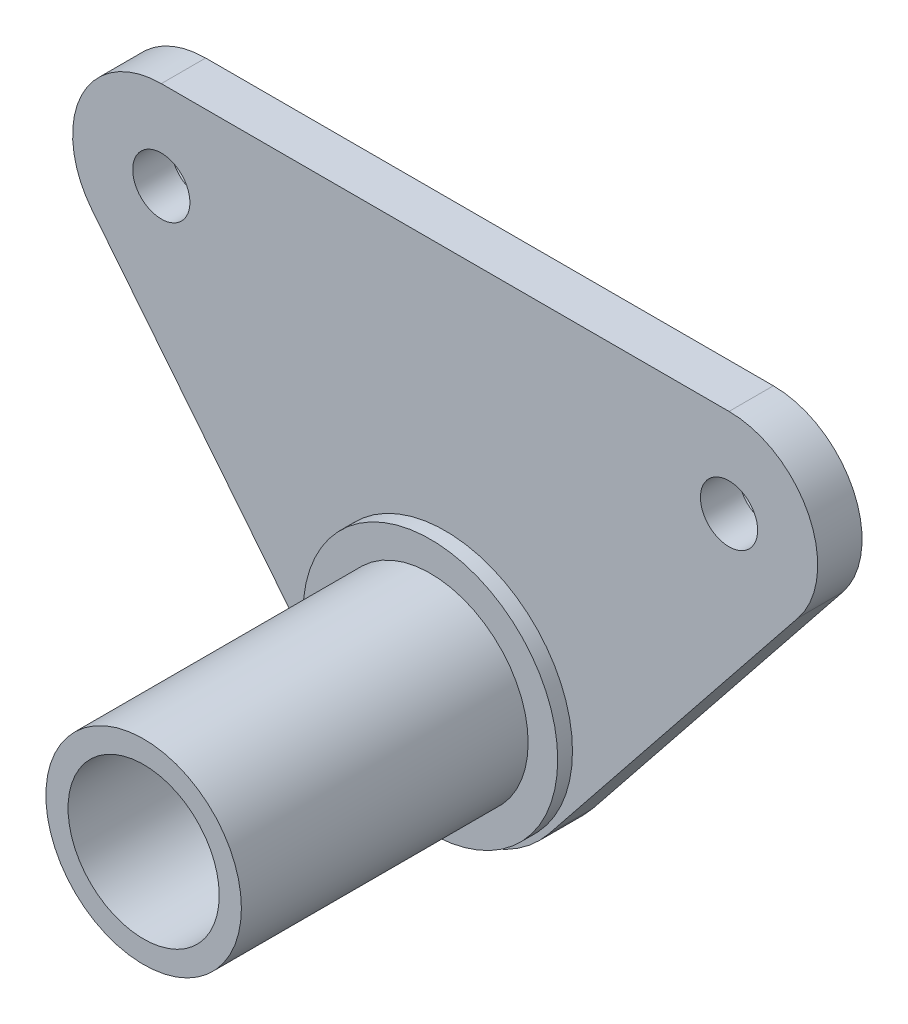
SolidWorks part; units mm, degrees
ref_plane "Front Plane" through (0, 0, 0) normal (0, 0, 1) x (1, 0, 0)
ref_plane "Top Plane" through (0, 0, 0) normal (0, 1, 0) x (1, 0, 0)
ref_plane "Right Plane" through (0, 0, 0) normal (1, 0, 0) x (0, 0, -1)
sketch "Sketch1" plane through (0, 0, 0) normal (0, 0, 1) x (1, 0, 0)
  line L0 (-24.39, 32.01) -> (24.39, 32.01)
  line L1 (-24.39, 28.2) -> (24.39, 28.2) construction
  line L2 (-28.2, 24.39) -> (-28.2, -24.39) construction
  line L3 (-24.39, -28.2) -> (24.39, -28.2) construction
  line L4 (28.2, 24.39) -> (28.2, -24.39) construction
  line L5 (-28.2, 28.2) -> (28.2, -28.2) construction
  line L6 (-28.2, -28.2) -> (28.2, 28.2) construction
  line L7 (32.01, 24.39) -> (32.01, -24.39) construction
  line L8 (-24.39, -32.01) -> (24.39, -32.01) construction
  line L9 (-32.01, 24.39) -> (-32.01, -24.39) construction
  line L10 (-23.57, 23.57) -> (0, -17.2544) construction
  line L11 (0, -17.2544) -> (23.57, 23.57) construction
  line L12 (-28.2, 23.57) -> (23.57, 23.57) construction
  line L14 (-8.9255, -7.14) -> (-30.3403, 19.63)
  line L15 (8.9255, -7.14) -> (30.3403, 19.63)
  circle A0 centre (-23.57, 23.57) radius 2.5 construction
  circle A1 centre (23.57, 23.57) radius 2.5 construction
  arc A2 (-32.01, 24.39) -> (-24.39, 32.01) centre (-24.39, 24.39) cw construction
  arc A3 (32.01, 24.39) -> (24.39, 32.01) centre (24.39, 24.39) ccw construction
  arc A4 (-28.2, 24.39) -> (-24.39, 28.2) centre (-24.39, 24.39) cw construction
  arc A5 (-28.2, -24.39) -> (-24.39, -28.2) centre (-24.39, -24.39) ccw construction
  arc A6 (28.2, -24.39) -> (24.39, -28.2) centre (24.39, -24.39) cw construction
  arc A7 (28.2, 24.39) -> (24.39, 28.2) centre (24.39, 24.39) ccw construction
  arc A8 (30.3403, 19.63) -> (24.39, 32.01) centre (24.39, 24.39) ccw
  arc A9 (32.01, -24.39) -> (24.39, -32.01) centre (24.39, -24.39) cw construction
  arc A10 (-32.01, -24.39) -> (-24.39, -32.01) centre (-24.39, -24.39) ccw construction
  arc A11 (-30.3403, 19.63) -> (-24.39, 32.01) centre (-24.39, 24.39) cw
  arc A12 (-8.9255, -7.14) -> (8.9255, -7.14) centre (0, 0) ccw
  point P0 (0, 0)
  dimension "D3" = 5
  dimension "D4" = 5
  dimension "D5" = 60
  dimension "D6" = 60
  dimension "D11" = 3.81
  dimension "D12" = 3.81
  dimension "D9" = 22.86
  dimension "D1" = 56.4
  dimension "D2" = 56.4
  dimension "D7" = 47.14
  dimension "D13" = 3.81
extrude "Boss-Extrude1" add sketch "Sketch1" along normal blind 3.81
sketch "Sketch2" plane through (0, 0, 3.81) normal (0, 0, 1) x (1, 0, 0)
  circle A0 centre (0, 0) radius 8.4
  circle A1 centre (0, 0) radius 6.495
  dimension "D1" = 16.8
  dimension "D2" = 1.905
extrude "Boss-Extrude2" add sketch "Sketch2" along normal blind 29.718 from surface starting at face at (0, 14.742, 0)
sketch "Sketch4" plane through (0, 0, 3.81) normal (0, 0, 1) x (1, 0, 0)
  circle A0 centre (0, 0) radius 6.98
extrude "Cut-Extrude2" cut sketch "Sketch4" against normal through all
sketch "Sketch5" plane through (0, 0, 3.81) normal (0, 0, 1) x (1, 0, 0)
  circle A1 centre (0, 0) radius 10.94
  arc A2 (8.4, 0) -> (8.4, 0) centre (0, 0) ccw
  circle A3 centre (0, 0) radius 8.4
  dimension "D1" = 0
  dimension "D2" = 2.54
extrude "Boss-Extrude3" add sketch "Sketch5" along normal blind 1.27 and the other way up to surface (3.81 mm away) other way up to face at (6.98, 0, 0)
hole_wizard "#8 Clearance Hole1" positions "Sketch7" profile "Sketch6" hole size "#8" standard "ANSI Inch"
sketch "Sketch7" plane through (0, 0, 3.81) normal (0, 0, 1) x (1, 0, 0)
  point P0 (-24.39, 24.39)
  point P3 (24.39, 24.39)
sketch "Sketch6" plane through (-24.39, 24.39, 3.81) normal (1, 0, 0) x (0, -1, 0)
  line L0 (0, 0) -> (0, 4.7786)
  line L1 (0, 4.7786) -> (2.4574, 3.302)
  line L2 (2.4574, 3.302) -> (2.4574, 0)
  line L5 (2.4574, 0) -> (0, 0)
  line L10 (0, 4.7786) -> (-2.4574, 3.302) construction
  line L11 (0, -6.35) -> (0, 107.95) construction
  dimension "Hole Dia." = 4.9149
  dimension "Hole Depth" = 3.302
  dimension "Drill Angle" = 118
